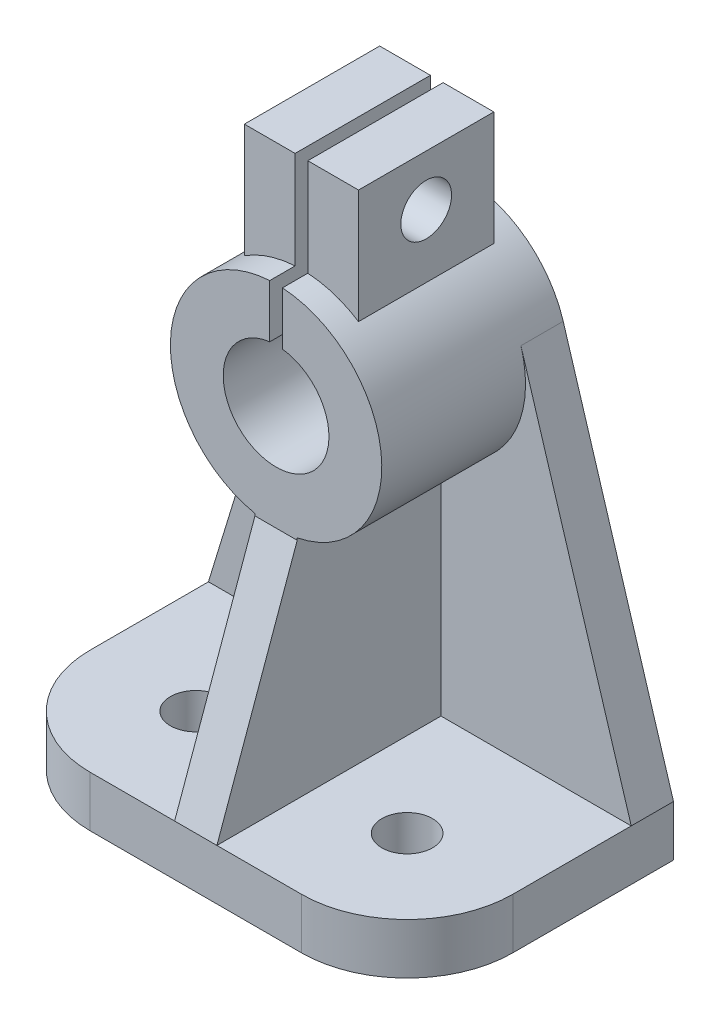
SolidWorks part; units mm, degrees
ref_plane "Front Plane" through (0, 0, 0) normal (0, 0, 1) x (1, 0, 0)
ref_plane "Top Plane" through (0, 0, 0) normal (0, 1, 0) x (1, 0, 0)
ref_plane "Right Plane" through (0, 0, 0) normal (1, 0, 0) x (0, 0, -1)
sketch "Sketch2" plane through (0, 0, 0) normal (0, 1, 0) x (1, 0, 0)
  line L1 (-50, 31.5) -> (50, 31.5)
  line L2 (-50, 31.5) -> (-50, -31.5)
  line L3 (-50, -31.5) -> (50, -31.5)
  line L4 (50, 31.5) -> (50, -31.5)
  line L5 (-50, 31.5) -> (50, -31.5) construction
  line L6 (-50, -31.5) -> (50, 31.5) construction
  point P0 (0, 0)
  dimension "D1" = 100
  dimension "D2" = 63
extrude "Boss-Extrude1" add sketch "Sketch2" along normal blind 12
fillet "Fillet1" radius 25 2 edges at (50, 6, 31.5) (-50, 6, 31.5)
sketch "Sketch3" plane through (0, 12, 0) normal (0, 1, 0) x (1, 0, 0)
  circle A0 centre (25, -6.5) radius 6
  circle A1 centre (-25, -6.5) radius 6
  dimension "D1" = 12
extrude "Cut-Extrude1" cut sketch "Sketch3" against normal through all contours A1 | A0
sketch "Sketch6" plane through (0, 0, -31.5) normal (0, 0, -1) x (-1, 0, 0)
  line L0 (0, 0) -> (0, 90) construction
  line L1 (-50, 12) -> (-23.9068, 97.312)
  line L2 (50, 12) -> (23.9068, 97.312)
  circle A0 centre (0, 90) radius 25
  line M6 (50, 12) -> (-50, 12)
  dimension "D1" = 50
  dimension "D2" = 90
extrude "Boss-Extrude2" add sketch "Sketch6" against normal blind 10 contours A0 | L0 L2 A0 M6 | L0 A0 L1 M6 region at (21.4549, 40.5565, -31.5) region at (-21.4549, 40.5565, -31.5) region at (19.5288, 75.5512, -31.5)
extrude "Boss-Extrude3" add sketch "Sketch6<3>" against normal blind 44 contours A0 region at (0, 90, -31.5)
sketch "Sketch6<3>" plane through (0, 0, -31.5) normal (0, 0, -1) x (-1, 0, 0) same geometry as "Sketch6"
sketch "Sketch7" plane through (0, 0, 12.5) normal (0, 0, 1) x (1, 0, 0)
  circle A0 centre (0, 90) radius 12.5
  point P3 (0, 0)
  dimension "D1" = 25
extrude "Cut-Extrude2" cut sketch "Sketch7" against normal through all
ref_plane "Plane2" through (0, 138, 0) normal (0, 1, 0) x (1, 0, 0)
sketch "Sketch8" plane through (0, 138, 0) normal (0, 1, 0) x (1, 0, 0)
  line L0 (0, 0) -> (0, 31.5) construction
  line L1 (23.9068, 31.5) -> (-23.9068, 31.5) construction
  line L3 (-13.5, 25.5) -> (13.5, 25.5)
  line L4 (-13.5, 25.5) -> (-13.5, -6.5)
  line L5 (-13.5, -6.5) -> (13.5, -6.5)
  line L6 (13.5, 25.5) -> (13.5, -6.5)
  line L7 (-13.5, 25.5) -> (13.5, -6.5) construction
  line L8 (-13.5, -6.5) -> (13.5, 25.5) construction
  point P5 (0, 9.5)
  dimension "D1" = 27
  dimension "D2" = 32
  dimension "D3" = 6
extrude "Boss-Extrude4" add sketch "Sketch8" against normal up to next
sketch "Sketch9" plane through (0, 0, 12.5) normal (0, 0, 1) x (1, 0, 0)
  line L0 (0, 65) -> (0, 138) construction
  line L1 (-13.5, 138) -> (13.5, 138) construction
  line L3 (1.5, 146.5533) -> (-1.5, 146.5533)
  line L4 (1.5, 146.5533) -> (1.5, 95.5678)
  line L5 (1.5, 95.5678) -> (-1.5, 95.5678)
  line L6 (-1.5, 146.5533) -> (-1.5, 95.5678)
  line L7 (1.5, 146.5533) -> (-1.5, 95.5678) construction
  line L8 (1.5, 95.5678) -> (-1.5, 146.5533) construction
  arc A0 (-23.9068, 97.312) -> (23.9068, 97.312) centre (0, 90) ccw construction
  point P7 (0, 121.0606)
  dimension "D1" = 3
extrude "Cut-Extrude3" cut sketch "Sketch9" against normal through all contours L3 L6 L5 L4
sketch "Sketch11" plane through (-13.5, 0, 0) normal (-1, 0, 0) x (0, 0, 1)
  line L0 (-9.5, 138) -> (-9.5, 111.0416) construction
  line L1 (-25.5, 138) -> (6.5, 138) construction
  line L2 (6.5, 111.0416) -> (-25.5, 111.0416) construction
  circle A1 centre (-9.5, 126) radius 6
  dimension "D1" = 12
  dimension "D2" = 12
sketch "Sketch13" plane through (-13.5, 0, 0) normal (-1, 0, 0) x (0, 0, 1)
extrude "Cut-Extrude4" cut sketch "Sketch11" against normal through all
sketch "Sketch14" plane through (0, 0, 0) normal (1, 0, 0) x (0, 0, -1)
  line L0 (-12.5, 65) -> (-31.5, 12)
  line L1 (-31.5, 12) -> (21.5, 12)
  line L2 (21.5, 12) -> (21.5, 97.312) construction
  line L3 (-6.5, 12) -> (21.5, 12) construction
  line L4 (21.5, 12) -> (21.5, 65)
  line L5 (21.5, 65) -> (-12.5, 65)
extrude "Boss-Extrude8" add sketch "Sketch14" along normal mid plane 10 separate body
sketch "Sketch16" plane through (0, 65, 0) normal (0, 1, 0) x (1, 0, 0)
  line L4 (-5, 21.5) -> (-5, -12.5)
  line L5 (-5, -12.5) -> (5, -12.5)
  line L6 (5, -12.5) -> (5, 21.5)
  line L7 (5, 21.5) -> (-5, 21.5)
  line L8 (-5, 21.5) -> (-5, -12.5)
  line L9 (-5, -12.5) -> (5, -12.5)
  line L10 (5, -12.5) -> (5, 21.5)
  line L11 (5, 21.5) -> (-5, 21.5)
  dimension "D1" = 0
extrude "Boss-Extrude9" add sketch "Sketch16" along direction (0, -1, 0) on the side of the normal up to surface up to face at (0, 105.0552, -13.75)
